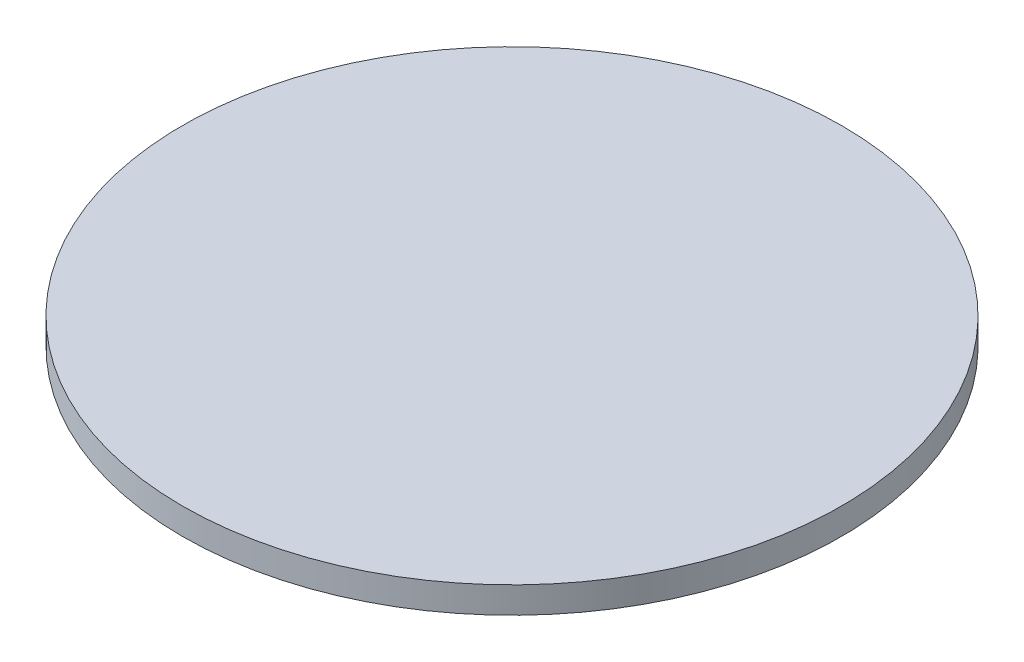
SolidWorks part; units mm, degrees
ref_plane "Front Plane" through (0, 0, 0) normal (0, 0, 1) x (1, 0, 0)
ref_plane "Top Plane" through (0, 0, 0) normal (0, 1, 0) x (1, 0, 0)
ref_plane "Right Plane" through (0, 0, 0) normal (1, 0, 0) x (0, 0, -1)
sketch "Sketch1" plane through (0, 0, 0) normal (0, 1, 0) x (1, 0, 0)
  circle A0 centre (0, 0) radius 150
extrude "Boss-Extrude1" add sketch "Sketch1" along normal blind 12
